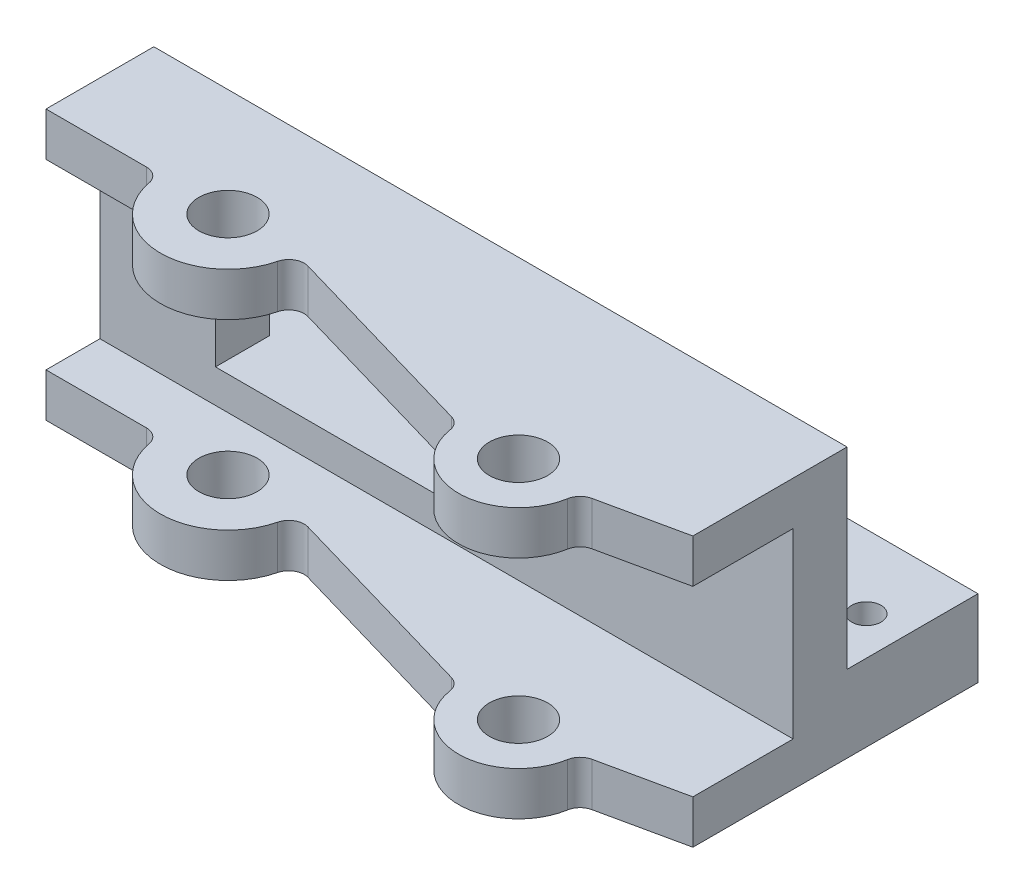
SolidWorks part; units mm, degrees
ref_plane "Front Plane" through (0, 0, 0) normal (0, 0, 1) x (1, 0, 0)
ref_plane "Top Plane" through (0, 0, 0) normal (0, 1, 0) x (1, 0, 0)
ref_plane "Right Plane" through (0, 0, 0) normal (1, 0, 0) x (0, 0, -1)
sketch "Sketch1" plane through (0, 0, 0) normal (0, 0, 1) x (1, 0, 0)
  line L1 (57.15, -22.225) -> (-57.15, -22.225)
  line L2 (57.15, -22.225) -> (57.15, 22.225)
  line L3 (57.15, 22.225) -> (-57.15, 22.225)
  line L4 (-57.15, -22.225) -> (-57.15, 22.225)
  line L5 (57.15, -22.225) -> (-57.15, 22.225) construction
  line L6 (57.15, 22.225) -> (-57.15, -22.225) construction
  point P0 (0, 0)
  dimension "D1" = 44.45
  dimension "D2" = 114.3
extrude "Boss-Extrude1" add sketch "Sketch1" along normal blind 62.23
sketch "Sketch2" plane through (0, 0, 62.23) normal (0, 0, 1) x (1, 0, 0)
  line L0 (-57.15, 22.225) -> (-57.15, -22.225) construction
  line L1 (57.15, -15.025) -> (-57.15, -15.025)
  line L2 (57.15, -15.025) -> (57.15, 15.025)
  line L3 (57.15, 15.025) -> (-57.15, 15.025)
  line L4 (-57.15, -15.025) -> (-57.15, 15.025)
  line L5 (57.15, -15.025) -> (-57.15, 15.025) construction
  line L6 (57.15, 15.025) -> (-57.15, -15.025) construction
  line L7 (57.15, 22.225) -> (-57.15, 22.225) construction
  point P0 (0, 0)
  dimension "D1" = 7.2
extrude "Cut-Extrude2" cut sketch "Sketch2" against normal blind 31.75
sketch "Sketch3" plane through (0, 0, 0) normal (0, 0, -1) x (-1, 0, 0)
  line L0 (-57.15, -22.225) -> (-57.15, 22.225) construction
  line L1 (57.15, 22.225) -> (-57.15, 22.225)
  line L2 (57.15, 22.225) -> (57.15, -9.525)
  line L3 (57.15, -9.525) -> (-57.15, -9.525)
  line L4 (-57.15, 22.225) -> (-57.15, -9.525)
  line L5 (57.15, -22.225) -> (-57.15, -22.225) construction
  dimension "D1" = 12.7
extrude "Cut-Extrude3" cut sketch "Sketch3" against normal blind 21.59
sketch "Sketch5" plane through (0, -22.225, 0) normal (0, -1, 0) x (1, 0, 0)
  line L0 (0, 12.06) -> (50.8, 12.06) construction
  line L1 (57.15, 21.59) -> (-57.15, 21.59) construction
  line L2 (57.15, 62.23) -> (57.15, 0) construction
  circle A0 centre (0, 12.06) radius 2.415
  circle A1 centre (50.8, 12.06) radius 2.415
  dimension "D3" = 4.83
  dimension "D4" = 6.35
  dimension "D1" = 9.53
  dimension "D2" = 50.8
extrude "Cut-Extrude4" cut sketch "Sketch5" against normal blind 25.4
sketch "Sketch6" plane through (0, 0, 21.59) normal (0, 0, -1) x (-1, 0, 0)
  line L0 (-53.215, -9.525) -> (2.415, -9.525) construction
  line L1 (-53.215, -9.525) -> (-53.215, -22.225) construction
  line L2 (2.415, -22.225) -> (2.415, -9.525) construction
  line L3 (-57.15, -9.525) -> (57.15, -9.525) construction
  line L4 (-30.6705, 6.477) -> (-30.6705, 1.651) construction
  line L5 (-32.893, 6.477) -> (-17.907, 6.477) construction
  line L6 (-22.987, 1.651) -> (-32.893, 1.651) construction
  line L7 (-32.893, 1.651) -> (-32.893, 6.477) construction
  circle A1 centre (-30.6705, 4.064) radius 2.2225
  point P6 (-30.0448, 4.064)
  dimension "D3" = 4.445
extrude "Cut-Extrude5" cut sketch "Sketch6" against normal blind 5.08
sketch "Sketch7" plane through (0, -22.225, 0) normal (0, -1, 0) x (1, 0, 0)
  line L0 (57.15, 62.23) -> (57.15, 0) construction
  line L1 (-57.15, 0) -> (57.15, 0) construction
  circle A0 centre (31.75, 50.36) radius 4.8
  circle A1 centre (-27.14, 39.37) radius 4.8
  point P8 (0, 0)
  point P9 (0, 0)
  point P10 (31.75, 45.0435)
  point P11 (31.6362, 42.5109)
  dimension "D1" = 9.6
  dimension "D2" = 25.4
  dimension "D3" = 39.37
  dimension "D4" = 9.6
  dimension "D5" = 58.89
  dimension "D6" = 10.99
extrude "Cut-Extrude6" cut sketch "Sketch7" against normal up to surface (44.45 mm away) up to face at (0, 22.225, 41.91)
sketch "Sketch9" plane through (0, 0, 30.48) normal (0, 0, 1) x (1, 0, 0)
  line L5 (57.15, 15.025) -> (-57.15, 15.025) construction
  line L6 (-38.1, 15.025) -> (6.35, 15.025)
  line L7 (-38.1, 15.025) -> (-38.1, -15.025)
  line L8 (-38.1, -15.025) -> (6.35, -15.025)
  line L9 (6.35, 15.025) -> (6.35, -15.025)
  line L10 (-57.15, -15.025) -> (57.15, -15.025) construction
  line L11 (-57.15, 15.025) -> (-57.15, -15.025) construction
  line L12 (57.15, -15.025) -> (57.15, 15.025) construction
  dimension "D1" = 50.8
  dimension "25in" = 19.05
extrude "Cut-Extrude7" cut sketch "Sketch9" against normal through all both and the other way through all
sketch "Sketch14" plane through (6.35, 0, 0) normal (-1, 0, 0) x (0, 0, 1)
  line L0 (0, -15.025) -> (30.48, -15.025) construction
  line L1 (21.59, -9.525) -> (0, -9.525)
  line L2 (21.59, -9.525) -> (21.59, -15.025)
  line L3 (21.59, -15.025) -> (0, -15.025)
  line L4 (0, -9.525) -> (0, -15.025)
extrude "Boss-Extrude2" add sketch "Sketch14" along normal up to next
sketch "Sketch16" plane through (0, -22.225, 0) normal (0, -1, 0) x (1, 0, 0)
  line L8 (-57.15, 62.23) -> (57.15, 62.23)
  line L9 (57.15, 62.23) -> (57.15, 47.0103)
  line L10 (57.15, 62.23) -> (57.15, 0) construction
  line L11 (-15.99, 39.37) -> (21.87, 50.36)
  line L12 (41.63, 50.36) -> (57.15, 47.0103)
  line L13 (-38.29, 39.37) -> (-57.15, 39.37)
  line L14 (-57.15, 62.23) -> (-57.15, 0) construction
  line L15 (-57.15, 39.37) -> (-57.15, 62.23)
  arc A2 (41.63, 50.36) -> (21.87, 50.36) centre (31.75, 50.36) ccw
  arc A3 (-15.99, 39.37) -> (-38.29, 39.37) centre (-27.14, 39.37) ccw
  circle A4 centre (-27.14, 39.37) radius 4.8 construction
  circle A5 centre (31.75, 50.36) radius 4.8 construction
  dimension "D1" = 6.35
  dimension "D2" = 5.08
extrude "Cut-Extrude8" cut sketch "Sketch16" against normal through all
fillet "Fillet1" radius 2.54 8 edges at (21.87, 18.625, 50.36) (41.63, -18.625, 50.36) (41.63, 18.625, 50.36) (-15.99, 18.625, 39.37) (-15.99, -18.625, 39.37) (21.87, -18.625, 50.36) (-38.29, -18.625, 39.37) (-38.29, 18.625, 39.37)
sketch "Sketch17" plane through (0, 0, 21.59) normal (0, 0, 1) x (1, 0, 0)
  line L1 (6.35, -15.025) -> (-38.1, -15.025)
  line L2 (6.35, -15.025) -> (6.35, -9.525)
  line L3 (6.35, -9.525) -> (-38.1, -9.525)
  line L4 (-38.1, -15.025) -> (-38.1, -9.525)
extrude "Boss-Extrude3" add sketch "Sketch17" along normal up to surface (8.89 mm away) up to face at (-47.625, 0, 30.48)
